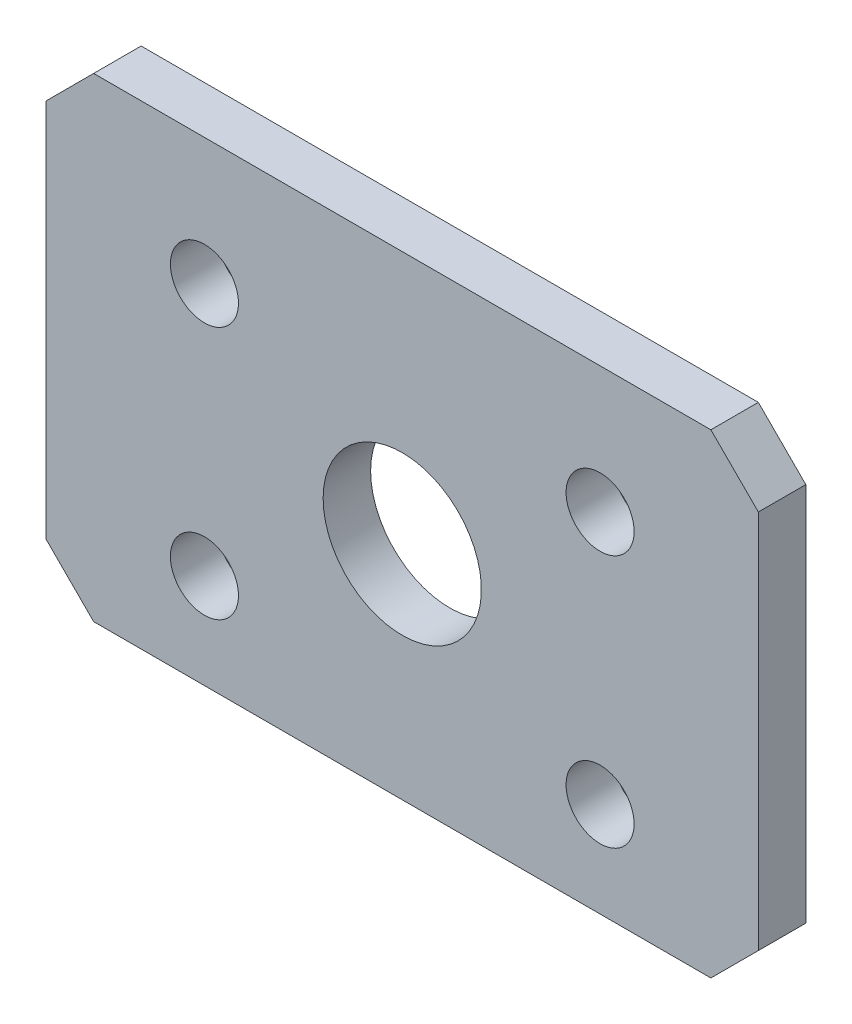
SolidWorks part; units mm, degrees
ref_plane "前视基准面" through (0, 0, 0) normal (0, 0, 1) x (1, 0, 0)
ref_plane "上视基准面" through (0, 0, 0) normal (0, 1, 0) x (1, 0, 0)
ref_plane "右视基准面" through (0, 0, 0) normal (1, 0, 0) x (0, 0, -1)
sketch "草图1" plane through (0, 0, 0) normal (0, 0, 1) x (1, 0, 0)
  line L1 (0, 0) -> (33, 0)
  line L2 (0, 0) -> (0, 47)
  line L3 (0, 47) -> (33, 47)
  line L4 (33, 0) -> (33, 47)
  circle A4 centre (16.5, 31) radius 5
  dimension "D6" = 10
  dimension "D3" = 33
  dimension "D4" = 47
extrude "凸台-拉伸1" add sketch "草图1" along normal blind 4
sketch "草图3" plane through (0, 0, 0) normal (0, 0, -1) x (-1, 0, 0)
  line L0 (0, -38) -> (-33, -38)
  line L1 (0, 47) -> (6, 47)
  line L2 (0, 47) -> (0, -38)
  line L4 (6, 47) -> (6, -63)
  line L5 (-33, 47) -> (-39, 47)
  line L6 (-33, 47) -> (-33, -38)
  line L8 (-39, 47) -> (-39, -63)
  line L9 (6, -63) -> (-6.25, -63)
  line L10 (-6.25, -63) -> (-6.25, -43)
  line L11 (-6.25, -43) -> (-26.75, -43)
  line L12 (-26.75, -43) -> (-26.75, -63)
  line L13 (-26.75, -63) -> (-39, -63)
  point P2 (-16.5, -38)
  point P14 (-16.5, -43)
  dimension "D1" = 6
  dimension "D2" = 6
  dimension "D3" = 25
  dimension "D4" = 110
  dimension "D5" = 20.5
  dimension "D6" = 20
extrude "凸台-拉伸2" add sketch "草图3" against normal blind 30
sketch "草图4" plane through (0, 0, 0) normal (0, 0, -1) x (-1, 0, 0)
  line L1 (-33, -38) -> (0, -38)
  line L2 (-33, -38) -> (-33, 0)
  line L3 (-33, 0) -> (0, 0)
  line L4 (0, -38) -> (0, 0)
extrude "凸台-拉伸3" add sketch "草图4" against normal up to surface (4 mm away) up to face at (16.5, 23.5, 4)
chamfer "倒角1" distance 3 angle 45 4 edges at (-6, -63, 15) (39, -63, 15) (-6, 47, 15) (39, 47, 15)
sketch "草图5" plane through (39, 0, 0) normal (1, 0, 0) x (0, 0, -1)
  line L0 (-30, 44) -> (-30, -60) construction
  line L1 (-30, -38) -> (-40, -38)
  line L2 (-30, -38) -> (-30, -8)
  line L3 (-30, -8) -> (-40, -8)
  line L4 (-40, -38) -> (-40, -8)
  line L5 (-30, -38) -> (-4, -38) construction
  dimension "D1" = 30
  dimension "D2" = 10
extrude "凸台-拉伸4" add sketch "草图5" against normal up to surface (6 mm away) up to face at (33, 4.5, 17)
sketch "草图6" plane through (39, 0, 0) normal (1, 0, 0) x (0, 0, -1)
  line L0 (-40, -8) -> (-40, -38) construction
  line L1 (-30, -8) -> (-40, -8) construction
  line L2 (-40, -38) -> (-30, -38) construction
  circle A0 centre (-11, -32) radius 2.15
  circle A1 centre (-35, -32) radius 2.15
  circle A2 centre (-11, -14) radius 2.15
  circle A3 centre (-35, -14) radius 2.15
  dimension "D5" = 4.3
  dimension "D1" = 5
  dimension "D2" = 6
  dimension "D3" = 6
  dimension "D4" = 24
extrude "切除-拉伸1" cut sketch "草图6" against normal through all
sketch "草图7" plane through (-6, 0, 0) normal (-1, 0, 0) x (0, 0, 1)
  line L0 (30, -63) -> (0, -63) construction
  line L1 (0, -60) -> (30, -60) construction
  circle A0 centre (15, -53) radius 2.15
  point P6 (15, -60)
  dimension "D2" = 4.3
  dimension "D1" = 10
extrude "切除-拉伸2" cut sketch "草图7" against normal blind 60
ref_plane "基准面1" through (39, 0, 0) normal (1, 0, 0) x (0, 0, -1)
mirror "镜向1" about plane through (39, 0, 0) normal (1, 0, 0) of bodies 111
sketch "草图8" plane through (39, 0, 0) normal (1, 0, 0) x (0, 0, -1)
  line L1 (57.1543, -72.0954) -> (-85.7181, -72.0954)
  line L2 (57.1543, -72.0954) -> (57.1543, 57.5557)
  line L3 (57.1543, 57.5557) -> (-85.7181, 57.5557)
  line L4 (-85.7181, -72.0954) -> (-85.7181, 57.5557)
extrude "切除-拉伸3" cut sketch "草图8" against normal through all
sketch "草图9" plane through (0, 0, 30) normal (0, 0, 1) x (1, 0, 0)
  line L1 (78, -38) -> (84, -38)
  line L2 (78, -38) -> (78, 47)
  line L3 (78, 47) -> (84, 47)
  line L4 (84, -38) -> (84, 47)
  line L5 (39, -8) -> (45, -8)
  line L6 (39, -8) -> (39, 47)
  line L7 (39, 47) -> (45, 47)
  line L8 (45, -8) -> (45, 47)
extrude "切除-拉伸4" cut sketch "草图9" against normal up to surface (26 mm away) up to face at (61.5, 4.5, 4)
sketch "草图10" plane through (0, 0, 4) normal (0, 0, 1) x (1, 0, 0)
  line L0 (42, 47) -> (39, 44)
  line L1 (39, 44) -> (39, 17)
  line L2 (39, -8) -> (39, 44) construction
  line L3 (39, 17) -> (84, 17)
  line L4 (84, -38) -> (84, 44) construction
  line L5 (84, 17) -> (84, 44)
  line L6 (84, 44) -> (81, 47)
  line L7 (81, 47) -> (42, 47)
  circle A0 centre (61.5, 31) radius 6.65
  dimension "D2" = 13.3
  dimension "D1" = 30
extrude "凸台-拉伸5" add sketch "草图10" along normal blind 5.2
sketch "草图11" plane through (39, 0, 0) normal (-1, 0, 0) x (0, 0, 1)
  line L0 (40, -8) -> (4, -8)
  line L1 (4, -8) -> (4, 17)
  line L2 (4, 17) -> (9.2, 17)
  line L3 (9.2, 17) -> (40, -8)
extrude "凸台-拉伸6" add sketch "草图11" against normal up to surface (6 mm away) up to face at (45, -26, 23.6)
chamfer "倒角2" distance 5.2 angle 45 1 edges at (64.5, 17, 4)
sketch "草图12" plane through (84, 0, 0) normal (1, 0, 0) x (0, 0, -1)
  line L0 (-30, -38) -> (-4, -38)
  line L1 (-4, -38) -> (-4, 11.8) construction
  line L2 (-4, -38) -> (-30, -38) construction
  line L3 (-4, -38) -> (-4, -13)
  line L4 (-4, -13) -> (-30, -38)
  circle A0 centre (-11, -32) radius 2.15
  dimension "D1" = 25
extrude "凸台-拉伸7" add sketch "草图12" against normal blind 6
sketch "草图13" plane through (0, 0, 9.2) normal (0, 0, 1) x (1, 0, 0)
  line L0 (39, 44) -> (39, 17) construction
  line L1 (84, 17) -> (84, 44) construction
  line L2 (81, 47) -> (42, 47) construction
  circle A0 centre (49, 39) radius 2.15
  circle A1 centre (49, 23) radius 2.15
  circle A2 centre (74, 39) radius 2.15
  circle A3 centre (74, 23) radius 2.15
  dimension "D4" = 16
  dimension "D5" = 4.3
  dimension "D1" = 10
  dimension "D2" = 10
  dimension "D3" = 8
extrude "切除-拉伸5" cut sketch "草图13" against normal through all
sketch "草图14" plane through (0, 0, 9.2) normal (0, 0, 1) x (1, 0, 0)
  line L1 (39, 17) -> (84, 17)
  line L2 (39, 17) -> (39, -64.9387)
  line L3 (39, -64.9387) -> (84, -64.9387)
  line L4 (84, 17) -> (84, -64.9387)
extrude "切除-拉伸6" cut sketch "草图14" against normal through all and the other way through all
sketch "草图15" plane through (0, 0, 9.2) normal (0, 0, 1) x (1, 0, 0)
  line L1 (39, 17) -> (87.9237, 17)
  line L2 (39, 17) -> (39, 51.9433)
  line L3 (39, 51.9433) -> (87.9237, 51.9433)
  line L4 (87.9237, 17) -> (87.9237, 51.9433)
extrude "切除-拉伸7" cut sketch "草图15" against normal offset from surface (6.2 mm away) 3 up to face at (61.5, 36, 0)
chamfer "倒角3" distance 3 angle 45 2 edges at (39, 17, 1.5) (84, 17, 1.5)
